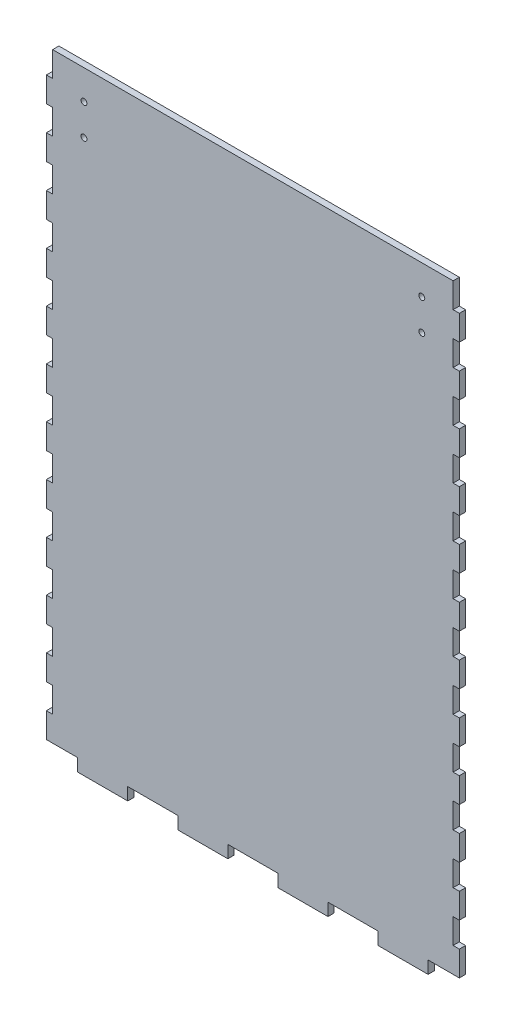
SolidWorks part; units mm, degrees
ref_plane "Front Plane" through (0, 0, 0) normal (0, 0, 1) x (1, 0, 0)
ref_plane "Top Plane" through (0, 0, 0) normal (0, 1, 0) x (1, 0, 0)
ref_plane "Right Plane" through (0, 0, 0) normal (1, 0, 0) x (0, 0, -1)
sketch "Sketch1" plane through (0, 0, 0) normal (0, 0, 1) x (1, 0, 0)
  line L0 (0, 0) -> (203.2, 0)
  line L1 (203.2, 0) -> (203.2, 304.8)
  line L2 (203.2, 304.8) -> (0, 304.8)
  line L3 (0, 304.8) -> (0, 0)
  dimension "D1" = 203.2
  dimension "D2" = 304.8
extrude "Boss-Extrude1" add sketch "Sketch1" along normal blind 3.175
sketch "Sketch2" plane through (0, 0, 3.175) normal (0, 0, 1) x (1, 0, 0)
  line L0 (0, 304.8) -> (-3.175, 304.8)
  line L1 (-3.175, 304.8) -> (-3.175, 292.1)
  line L2 (-3.175, 292.1) -> (0, 292.1)
  line L3 (0, 304.8) -> (0, 0) construction
  line L4 (0, 292.1) -> (0, 304.8)
  line L5 (101.6, 304.8) -> (101.6, 0) construction
  line L6 (203.2, 304.8) -> (0, 304.8) construction
  line L7 (0, 0) -> (203.2, 0) construction
  line L8 (206.375, 292.1) -> (203.2, 292.1)
  line L9 (206.375, 304.8) -> (206.375, 292.1)
  line L10 (203.2, 304.8) -> (206.375, 304.8)
  line L11 (203.2, 292.1) -> (203.2, 304.8)
  line L12 (0, 266.7) -> (0, 279.4)
  line L13 (0, 279.4) -> (-3.175, 279.4)
  line L14 (-3.175, 279.4) -> (-3.175, 266.7)
  line L15 (-3.175, 266.7) -> (0, 266.7)
  line L16 (206.375, 266.7) -> (203.2, 266.7)
  line L17 (203.2, 266.7) -> (203.2, 279.4)
  line L18 (203.2, 279.4) -> (206.375, 279.4)
  line L19 (206.375, 279.4) -> (206.375, 266.7)
  line L20 (0, 241.3) -> (0, 254)
  line L21 (0, 254) -> (-3.175, 254)
  line L22 (-3.175, 254) -> (-3.175, 241.3)
  line L23 (-3.175, 241.3) -> (0, 241.3)
  line L24 (206.375, 241.3) -> (203.2, 241.3)
  line L25 (203.2, 241.3) -> (203.2, 254)
  line L26 (203.2, 254) -> (206.375, 254)
  line L27 (206.375, 254) -> (206.375, 241.3)
  line L28 (0, 215.9) -> (0, 228.6)
  line L29 (0, 228.6) -> (-3.175, 228.6)
  line L30 (-3.175, 228.6) -> (-3.175, 215.9)
  line L31 (-3.175, 215.9) -> (0, 215.9)
  line L32 (206.375, 215.9) -> (203.2, 215.9)
  line L33 (203.2, 215.9) -> (203.2, 228.6)
  line L34 (203.2, 228.6) -> (206.375, 228.6)
  line L35 (206.375, 228.6) -> (206.375, 215.9)
  line L36 (0, 190.5) -> (0, 203.2)
  line L37 (0, 203.2) -> (-3.175, 203.2)
  line L38 (-3.175, 203.2) -> (-3.175, 190.5)
  line L39 (-3.175, 190.5) -> (0, 190.5)
  line L40 (206.375, 190.5) -> (203.2, 190.5)
  line L41 (203.2, 190.5) -> (203.2, 203.2)
  line L42 (203.2, 203.2) -> (206.375, 203.2)
  line L43 (206.375, 203.2) -> (206.375, 190.5)
  line L44 (0, 165.1) -> (0, 177.8)
  line L45 (0, 177.8) -> (-3.175, 177.8)
  line L46 (-3.175, 177.8) -> (-3.175, 165.1)
  line L47 (-3.175, 165.1) -> (0, 165.1)
  line L48 (206.375, 165.1) -> (203.2, 165.1)
  line L49 (203.2, 165.1) -> (203.2, 177.8)
  line L50 (203.2, 177.8) -> (206.375, 177.8)
  line L51 (206.375, 177.8) -> (206.375, 165.1)
  line L52 (0, 139.7) -> (0, 152.4)
  line L53 (0, 152.4) -> (-3.175, 152.4)
  line L54 (-3.175, 152.4) -> (-3.175, 139.7)
  line L55 (-3.175, 139.7) -> (0, 139.7)
  line L56 (206.375, 139.7) -> (203.2, 139.7)
  line L57 (203.2, 139.7) -> (203.2, 152.4)
  line L58 (203.2, 152.4) -> (206.375, 152.4)
  line L59 (206.375, 152.4) -> (206.375, 139.7)
  line L60 (0, 114.3) -> (0, 127)
  line L61 (0, 127) -> (-3.175, 127)
  line L62 (-3.175, 127) -> (-3.175, 114.3)
  line L63 (-3.175, 114.3) -> (0, 114.3)
  line L64 (206.375, 114.3) -> (203.2, 114.3)
  line L65 (203.2, 114.3) -> (203.2, 127)
  line L66 (203.2, 127) -> (206.375, 127)
  line L67 (206.375, 127) -> (206.375, 114.3)
  line L68 (0, 88.9) -> (0, 101.6)
  line L69 (0, 101.6) -> (-3.175, 101.6)
  line L70 (-3.175, 101.6) -> (-3.175, 88.9)
  line L71 (-3.175, 88.9) -> (0, 88.9)
  line L72 (206.375, 88.9) -> (203.2, 88.9)
  line L73 (203.2, 88.9) -> (203.2, 101.6)
  line L74 (203.2, 101.6) -> (206.375, 101.6)
  line L75 (206.375, 101.6) -> (206.375, 88.9)
  line L76 (0, 63.5) -> (0, 76.2)
  line L77 (0, 76.2) -> (-3.175, 76.2)
  line L78 (-3.175, 76.2) -> (-3.175, 63.5)
  line L79 (-3.175, 63.5) -> (0, 63.5)
  line L80 (206.375, 63.5) -> (203.2, 63.5)
  line L81 (203.2, 63.5) -> (203.2, 76.2)
  line L82 (203.2, 76.2) -> (206.375, 76.2)
  line L83 (206.375, 76.2) -> (206.375, 63.5)
  line L84 (0, 38.1) -> (0, 50.8)
  line L85 (0, 50.8) -> (-3.175, 50.8)
  line L86 (-3.175, 50.8) -> (-3.175, 38.1)
  line L87 (-3.175, 38.1) -> (0, 38.1)
  line L88 (206.375, 38.1) -> (203.2, 38.1)
  line L89 (203.2, 38.1) -> (203.2, 50.8)
  line L90 (203.2, 50.8) -> (206.375, 50.8)
  line L91 (206.375, 50.8) -> (206.375, 38.1)
  line L92 (0, 12.7) -> (0, 25.4)
  line L93 (0, 25.4) -> (-3.175, 25.4)
  line L94 (-3.175, 25.4) -> (-3.175, 12.7)
  line L95 (-3.175, 12.7) -> (0, 12.7)
  line L96 (206.375, 12.7) -> (203.2, 12.7)
  line L97 (203.2, 12.7) -> (203.2, 25.4)
  line L98 (203.2, 25.4) -> (206.375, 25.4)
  line L99 (206.375, 25.4) -> (206.375, 12.7)
  line L100 (0, 292.1) -> (0, 266.7) construction
  line L101 (12.7, 0) -> (12.7, -6.35)
  line L102 (12.7, -6.35) -> (38.1, -6.35)
  line L103 (38.1, -6.35) -> (38.1, 0)
  line L104 (38.1, 0) -> (12.7, 0)
  line L105 (88.9, 0) -> (63.5, 0)
  line L106 (63.5, 0) -> (63.5, -6.35)
  line L107 (63.5, -6.35) -> (88.9, -6.35)
  line L108 (88.9, -6.35) -> (88.9, 0)
  line L109 (139.7, 0) -> (114.3, 0)
  line L110 (114.3, 0) -> (114.3, -6.35)
  line L111 (114.3, -6.35) -> (139.7, -6.35)
  line L112 (139.7, -6.35) -> (139.7, 0)
  line L113 (190.5, 0) -> (165.1, 0)
  line L114 (165.1, 0) -> (165.1, -6.35)
  line L115 (165.1, -6.35) -> (190.5, -6.35)
  line L116 (190.5, -6.35) -> (190.5, 0)
  line L117 (38.1, 0) -> (88.9, 0) construction
  dimension "D1" = 3.175
  dimension "D2" = 12.7
  dimension "D4" = 25.4
  dimension "D5" = 12.7
  dimension "D6" = 6.35
  dimension "D7" = 25.4
  dimension "D9" = 50.8
  dimension "D3" = 12
  dimension "D8" = 4
extrude "Boss-Extrude2" [suppressed] add sketch "Sketch2" against normal up to surface (3.175 mm away) up to face at (101.6, 152.4, 0)
sketch "Sketch3" plane through (0, 0, 3.175) normal (0, 0, 1) x (1, 0, 0)
  line L0 (0, 0) -> (-3.175, 0)
  line L1 (-3.175, 0) -> (-3.175, 12.7)
  line L2 (-3.175, 12.7) -> (0, 12.7)
  line L3 (0, 304.8) -> (0, 0) construction
  line L4 (0, 12.7) -> (0, 0)
  line L5 (101.6, 304.8) -> (101.6, 0) construction
  line L6 (203.2, 304.8) -> (0, 304.8) construction
  line L7 (0, 0) -> (203.2, 0) construction
  line L8 (206.375, 12.7) -> (203.2, 12.7)
  line L9 (206.375, 0) -> (206.375, 12.7)
  line L10 (203.2, 0) -> (206.375, 0)
  line L11 (203.2, 12.7) -> (203.2, 0)
  line L12 (0, 38.1) -> (0, 25.4)
  line L13 (0, 25.4) -> (-3.175, 25.4)
  line L14 (-3.175, 25.4) -> (-3.175, 38.1)
  line L15 (-3.175, 38.1) -> (0, 38.1)
  line L16 (206.375, 38.1) -> (203.2, 38.1)
  line L17 (203.2, 38.1) -> (203.2, 25.4)
  line L18 (203.2, 25.4) -> (206.375, 25.4)
  line L19 (206.375, 25.4) -> (206.375, 38.1)
  line L20 (0, 63.5) -> (0, 50.8)
  line L21 (0, 50.8) -> (-3.175, 50.8)
  line L22 (-3.175, 50.8) -> (-3.175, 63.5)
  line L23 (-3.175, 63.5) -> (0, 63.5)
  line L24 (206.375, 63.5) -> (203.2, 63.5)
  line L25 (203.2, 63.5) -> (203.2, 50.8)
  line L26 (203.2, 50.8) -> (206.375, 50.8)
  line L27 (206.375, 50.8) -> (206.375, 63.5)
  line L28 (0, 88.9) -> (0, 76.2)
  line L29 (0, 76.2) -> (-3.175, 76.2)
  line L30 (-3.175, 76.2) -> (-3.175, 88.9)
  line L31 (-3.175, 88.9) -> (0, 88.9)
  line L32 (206.375, 88.9) -> (203.2, 88.9)
  line L33 (203.2, 88.9) -> (203.2, 76.2)
  line L34 (203.2, 76.2) -> (206.375, 76.2)
  line L35 (206.375, 76.2) -> (206.375, 88.9)
  line L36 (0, 114.3) -> (0, 101.6)
  line L37 (0, 101.6) -> (-3.175, 101.6)
  line L38 (-3.175, 101.6) -> (-3.175, 114.3)
  line L39 (-3.175, 114.3) -> (0, 114.3)
  line L40 (206.375, 114.3) -> (203.2, 114.3)
  line L41 (203.2, 114.3) -> (203.2, 101.6)
  line L42 (203.2, 101.6) -> (206.375, 101.6)
  line L43 (206.375, 101.6) -> (206.375, 114.3)
  line L44 (0, 139.7) -> (0, 127)
  line L45 (0, 127) -> (-3.175, 127)
  line L46 (-3.175, 127) -> (-3.175, 139.7)
  line L47 (-3.175, 139.7) -> (0, 139.7)
  line L48 (206.375, 139.7) -> (203.2, 139.7)
  line L49 (203.2, 139.7) -> (203.2, 127)
  line L50 (203.2, 127) -> (206.375, 127)
  line L51 (206.375, 127) -> (206.375, 139.7)
  line L52 (0, 165.1) -> (0, 152.4)
  line L53 (0, 152.4) -> (-3.175, 152.4)
  line L54 (-3.175, 152.4) -> (-3.175, 165.1)
  line L55 (-3.175, 165.1) -> (0, 165.1)
  line L56 (206.375, 165.1) -> (203.2, 165.1)
  line L57 (203.2, 165.1) -> (203.2, 152.4)
  line L58 (203.2, 152.4) -> (206.375, 152.4)
  line L59 (206.375, 152.4) -> (206.375, 165.1)
  line L60 (0, 190.5) -> (0, 177.8)
  line L61 (0, 177.8) -> (-3.175, 177.8)
  line L62 (-3.175, 177.8) -> (-3.175, 190.5)
  line L63 (-3.175, 190.5) -> (0, 190.5)
  line L64 (206.375, 190.5) -> (203.2, 190.5)
  line L65 (203.2, 190.5) -> (203.2, 177.8)
  line L66 (203.2, 177.8) -> (206.375, 177.8)
  line L67 (206.375, 177.8) -> (206.375, 190.5)
  line L68 (0, 215.9) -> (0, 203.2)
  line L69 (0, 203.2) -> (-3.175, 203.2)
  line L70 (-3.175, 203.2) -> (-3.175, 215.9)
  line L71 (-3.175, 215.9) -> (0, 215.9)
  line L72 (206.375, 215.9) -> (203.2, 215.9)
  line L73 (203.2, 215.9) -> (203.2, 203.2)
  line L74 (203.2, 203.2) -> (206.375, 203.2)
  line L75 (206.375, 203.2) -> (206.375, 215.9)
  line L76 (0, 241.3) -> (0, 228.6)
  line L77 (0, 228.6) -> (-3.175, 228.6)
  line L78 (-3.175, 228.6) -> (-3.175, 241.3)
  line L79 (-3.175, 241.3) -> (0, 241.3)
  line L80 (206.375, 241.3) -> (203.2, 241.3)
  line L81 (203.2, 241.3) -> (203.2, 228.6)
  line L82 (203.2, 228.6) -> (206.375, 228.6)
  line L83 (206.375, 228.6) -> (206.375, 241.3)
  line L84 (0, 266.7) -> (0, 254)
  line L85 (0, 254) -> (-3.175, 254)
  line L86 (-3.175, 254) -> (-3.175, 266.7)
  line L87 (-3.175, 266.7) -> (0, 266.7)
  line L88 (206.375, 266.7) -> (203.2, 266.7)
  line L89 (203.2, 266.7) -> (203.2, 254)
  line L90 (203.2, 254) -> (206.375, 254)
  line L91 (206.375, 254) -> (206.375, 266.7)
  line L92 (0, 292.1) -> (0, 279.4)
  line L93 (0, 279.4) -> (-3.175, 279.4)
  line L94 (-3.175, 279.4) -> (-3.175, 292.1)
  line L95 (-3.175, 292.1) -> (0, 292.1)
  line L96 (206.375, 292.1) -> (203.2, 292.1)
  line L97 (203.2, 292.1) -> (203.2, 279.4)
  line L98 (203.2, 279.4) -> (206.375, 279.4)
  line L99 (206.375, 279.4) -> (206.375, 292.1)
  line L100 (0, 12.7) -> (0, 38.1) construction
  line L101 (12.7, 0) -> (12.7, -6.35)
  line L102 (12.7, -6.35) -> (38.1, -6.35)
  line L103 (38.1, -6.35) -> (38.1, 0)
  line L104 (38.1, 0) -> (12.7, 0)
  line L105 (88.9, 0) -> (63.5, 0)
  line L106 (63.5, 0) -> (63.5, -6.35)
  line L107 (63.5, -6.35) -> (88.9, -6.35)
  line L108 (88.9, -6.35) -> (88.9, 0)
  line L109 (139.7, 0) -> (114.3, 0)
  line L110 (114.3, 0) -> (114.3, -6.35)
  line L111 (114.3, -6.35) -> (139.7, -6.35)
  line L112 (139.7, -6.35) -> (139.7, 0)
  line L113 (190.5, 0) -> (165.1, 0)
  line L114 (165.1, 0) -> (165.1, -6.35)
  line L115 (165.1, -6.35) -> (190.5, -6.35)
  line L116 (190.5, -6.35) -> (190.5, 0)
  line L117 (38.1, 0) -> (88.9, 0) construction
  dimension "D1" = 3.175
  dimension "D2" = 12.7
  dimension "D9" = 50.8
  dimension "D3" = 12
  dimension "D8" = 4
  dimension "D4" = 25.4
  dimension "D5" = 6.35
  dimension "D6" = 25.4
  dimension "D7" = 12.7
sketch "Sketch4" [suppressed] plane through (0, 0, 3.175) normal (0, 0, 1) x (1, 0, 0)
  line L0 (50.8, 33.5) -> (50.8, 66.5) construction
  line L1 (34.3, 50) -> (67.3, 50) construction
  line L2 (0, 12.7) -> (0, 0) construction
  line L3 (88.9, 0) -> (114.3, 0) construction
  circle A0 centre (50.8, 50) radius 16.5
  circle A1 centre (25.8, 75) radius 1.5
  circle A5 centre (75.8, 75) radius 1.5
  circle A6 centre (75.8, 25) radius 1.5
  circle A7 centre (25.8, 25) radius 1.5
  dimension "D5" = 33
  dimension "D6" = 3
  dimension "D1" = 50
  dimension "D2" = 50
  dimension "D3" = 60
  dimension "D4" = 50
extrude "Cut-Extrude1" [suppressed] cut sketch "Sketch4" against normal up to surface (3.175 mm away) up to face at (101.6, 152.4, 0)
sketch "Sketch5" [suppressed] plane through (0, 0, 0) normal (0, 0, -1) x (-1, 0, 0)
  line L1 (-206.375, 304.8) -> (-206.375, 292.1) construction
  line L2 (-206.375, 304.8) -> (3.175, 304.8) construction
  line L3 (-101.6, 304.8) -> (-101.6, 0) construction
  line L4 (-88.9, 0) -> (-114.3, 0) construction
  circle A1 centre (-187.325, 289.8) radius 1.5
  circle A2 centre (-187.325, 274.05) radius 1.5
  circle A3 centre (-15.875, 274.05) radius 1.5
  circle A4 centre (-15.875, 289.8) radius 1.5
  dimension "D1" = 3
  dimension "D2" = 3
  dimension "D3" = 15.75
  dimension "D4" = 19.05
  dimension "D5" = 15
extrude "Cut-Extrude2" [suppressed] cut sketch "Sketch5" against normal up to surface (3.175 mm away) up to face at (101.6, 152.4, 3.175)
extrude "Boss-Extrude4" add sketch "Sketch3" against normal up to surface (3.175 mm away) up to face at (101.6, 152.4, 0)
sketch "Sketch6" plane through (0, 0, 0) normal (0, 0, -1) x (-1, 0, 0)
  line L1 (-203.2, 304.8) -> (0, 304.8) construction
  line L2 (-101.6, 304.8) -> (-101.6, 0) construction
  line L3 (-88.9, 0) -> (-114.3, 0) construction
  line L4 (-206.375, 292.1) -> (-206.375, 279.4) construction
  circle A0 centre (-187.325, 289.8) radius 1.5
  circle A1 centre (-187.325, 274.05) radius 1.5
  circle A2 centre (-15.875, 274.05) radius 1.5
  circle A3 centre (-15.875, 289.8) radius 1.5
  dimension "D1" = 3
  dimension "D2" = 3
  dimension "D3" = 19.05
  dimension "D4" = 15
  dimension "D5" = 15.75
extrude "Cut-Extrude3" cut sketch "Sketch6" against normal up to surface (3.175 mm away) up to face at (101.6, 130.175, 3.175)
equation "\"wall_thickness\"= 0.125in"
equation "\"base_thickness\"= 0.25in"
equation "\"D1@Boss-Extrude1\"=\"wall_thickness\""
equation "\"D1@Sketch2\"=\"wall_thickness\""
equation "\"D6@Sketch2\"=\"base_thickness\""
equation "\"D1@Sketch3\"=\"wall_thickness\""
equation "\"D5@Sketch3\"=\"base_thickness\""
